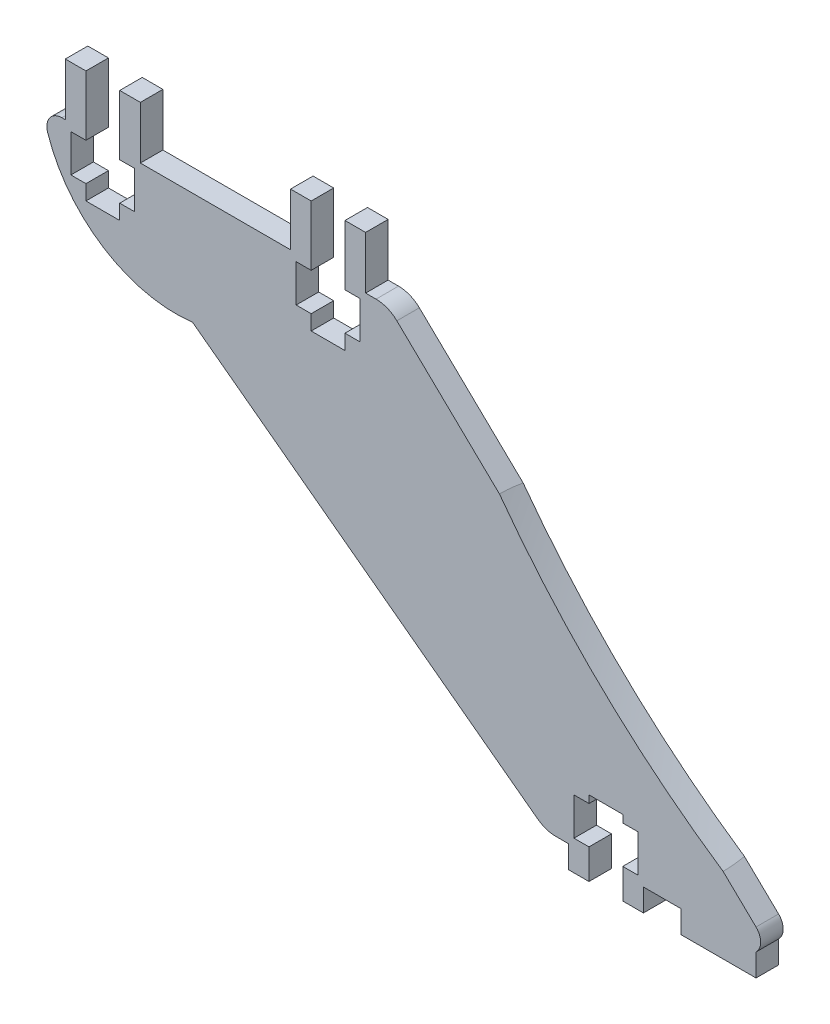
SolidWorks part; units mm, degrees
ref_plane "前视基准面" through (0, 0, 0) normal (0, 0, 1) x (1, 0, 0)
ref_plane "上视基准面" through (0, 0, 0) normal (0, 1, 0) x (1, 0, 0)
ref_plane "右视基准面" through (0, 0, 0) normal (1, 0, 0) x (0, 0, -1)
other "Configuration Table"
sketch "草图1" plane through (0, 0, 0) normal (0, 0, 1) x (1, 0, 0)
  line L0 (0, 0) -> (46, 0)
  line L1 (46, 0) -> (98, -50)
  line L2 (98, -50) -> (67, -50)
  line L3 (67, -50) -> (0, 0)
  line L5 (3, 0) -> (13, 0)
  line L6 (3, 0) -> (3, 7)
  line L7 (3, 7) -> (13, 7)
  line L8 (13, 0) -> (13, 7)
  line L9 (43, 0) -> (33, 0)
  line L10 (43, 0) -> (43, 7)
  line L11 (43, 7) -> (33, 7)
  line L12 (33, 0) -> (33, 7)
  line L13 (70, -50) -> (80, -50)
  line L14 (70, -50) -> (70, -53)
  line L15 (70, -53) -> (80, -53)
  line L16 (80, -50) -> (80, -53)
  line L17 (95, -50) -> (85, -50)
  line L18 (95, -50) -> (95, -53)
  line L19 (95, -53) -> (85, -53)
  line L20 (85, -50) -> (85, -53)
  dimension "D1" = 52
  dimension "D2" = 67
  dimension "D3" = 50
  dimension "D4" = 46
  dimension "D5" = 7
  dimension "D6" = 10
  dimension "D7" = 7
  dimension "D8" = 10
  dimension "D9" = 3
  dimension "D10" = 10
  dimension "D11" = 3
  dimension "D12" = 10
  dimension "D13" = 3
  dimension "D14" = 3
  dimension "D15" = 3
  dimension "D16" = 3
extrude "凸台-拉伸1" add sketch "草图1" along normal mid plane 3 contours L2 L20 L19 L18 | L3 L2 L1 L0 | L12 L0 L10 L11 | L0 L8 L7 L6 | L15 L16 L13 L14 region at (50.8182, -23.3766, 0) region at (8, 3.5, 0) region at (38, 3.5, 0) region at (90, -51.5, 0)
fillet "圆角1" radius 4 2 edges at (67, -50, 0) (46, 0, 0)
sketch "草图5" plane through (0, 0, 1.5) normal (0, 0, 1) x (1, 0, 0)
  line L0 (65.9357, -49.2057) -> (0, 0) construction
  line L1 (19.9555, -14.8922) -> (0, 0)
  arc A0 (0, 0) -> (19.9555, -14.8922) centre (17.7529, 2.9725) ccw
  point P2 (0.0707, -0.0528)
  line M17 (0, 0) -> (65.9357, -49.2057)
  dimension "D1" = 18
  dimension "D2" = 13
extrude "凸台-拉伸2" add sketch "草图5" against normal blind 3 contours L1 A0 M17 region at (8.7661, -9.0697, 1.5)
sketch "草图2" plane through (0, 0, 1.5) normal (0, 0, 1) x (1, 0, 0)
  line L0 (72.75, -53) -> (72.75, -49)
  line L1 (70, -53) -> (80, -53) construction
  line L2 (72.75, -49) -> (70.75, -49)
  line L3 (70.75, -49) -> (70.75, -44)
  line L4 (70.75, -44) -> (72.75, -44)
  line L5 (72.75, -44) -> (72.75, -43)
  line L6 (72.75, -43) -> (77.25, -43)
  line L7 (77.25, -43) -> (77.25, -44)
  line L8 (77.25, -44) -> (79.25, -44)
  line L9 (79.25, -44) -> (79.25, -49)
  line L10 (79.25, -49) -> (77.25, -49)
  line L11 (77.25, -49) -> (77.25, -53)
  line L12 (70, -50) -> (70, -53) construction
  line L13 (72.75, -53) -> (77.25, -53)
  line L14 (35.75, 7) -> (35.75, -1)
  line L15 (43, 7) -> (33, 7) construction
  line L16 (35.75, -1) -> (33.75, -1)
  line L17 (33.75, -1) -> (33.75, -6)
  line L18 (33.75, -6) -> (35.75, -6)
  line L19 (35.75, -6) -> (35.75, -8)
  line L20 (35.75, -8) -> (40.25, -8)
  line L21 (40.25, -8) -> (40.25, -6)
  line L22 (40.25, -6) -> (42.25, -6)
  line L23 (42.25, -6) -> (42.25, -1)
  line L24 (42.25, -1) -> (40.25, -1)
  line L25 (40.25, -1) -> (40.25, 7)
  line L26 (40.25, 7) -> (35.75, 7)
  line L27 (33, 0) -> (33, 7) construction
  line L30 (10.25, 7) -> (5.75, 7)
  line L31 (5.75, 7) -> (5.75, -1)
  line L32 (5.75, -1) -> (3.75, -1)
  line L33 (3.75, -1) -> (3.75, -6)
  line L34 (3.75, -6) -> (5.75, -6)
  line L35 (5.75, -6) -> (5.75, -8)
  line L36 (5.75, -8) -> (10.25, -8)
  line L37 (10.25, -8) -> (10.25, -6)
  line L38 (10.25, -6) -> (12.25, -6)
  line L39 (12.25, -6) -> (12.25, -1)
  line L40 (12.25, -1) -> (10.25, -1)
  line L41 (10.25, -1) -> (10.25, 7)
  point P14 (75, -43)
  point P31 (38, -8)
  dimension "D1" = 4
  dimension "D2" = 2
  dimension "D3" = 5
  dimension "D4" = 2
  dimension "D5" = 1
  dimension "D6" = 4.5
  dimension "D7" = 1
  dimension "D8" = 2
  dimension "D9" = 5
  dimension "D10" = 2
  dimension "D11" = 5
  dimension "D12" = 8
  dimension "D13" = 2
  dimension "D14" = 5
  dimension "D15" = 2
  dimension "D16" = 2
  dimension "D17" = 4.5
  dimension "D18" = 2
  dimension "D19" = 2
  dimension "D20" = 5
  dimension "D21" = 2
  dimension "D22" = 5
  dimension "D23" = 2
  dimension "D24" = 30
extrude "切除-拉伸1" cut sketch "草图2" against normal through all
sketch "草图3" plane through (0, 0, 1.5) normal (0, 0, 1) x (1, 0, 0)
  line L0 (158, -1021.2791) -> (158, 48978.7209) construction
  line L1 (43, 0) -> (43, 7) construction
  line L2 (13, 0) -> (33, 0) construction
  line L3 (158, -63.5) -> (158, 177.5)
  arc A0 (158, 177.5) -> (158, -63.5) centre (158, 57) ccw
  dimension "D2" = 57
  dimension "D3" = 241
  dimension "D1" = 115
revolve "切除-旋转3" cut sketch "草图3" angle 360 about L0
fillet "圆角2" radius 2 2 edges at (98, -50, 0) (0, 0, 0)
